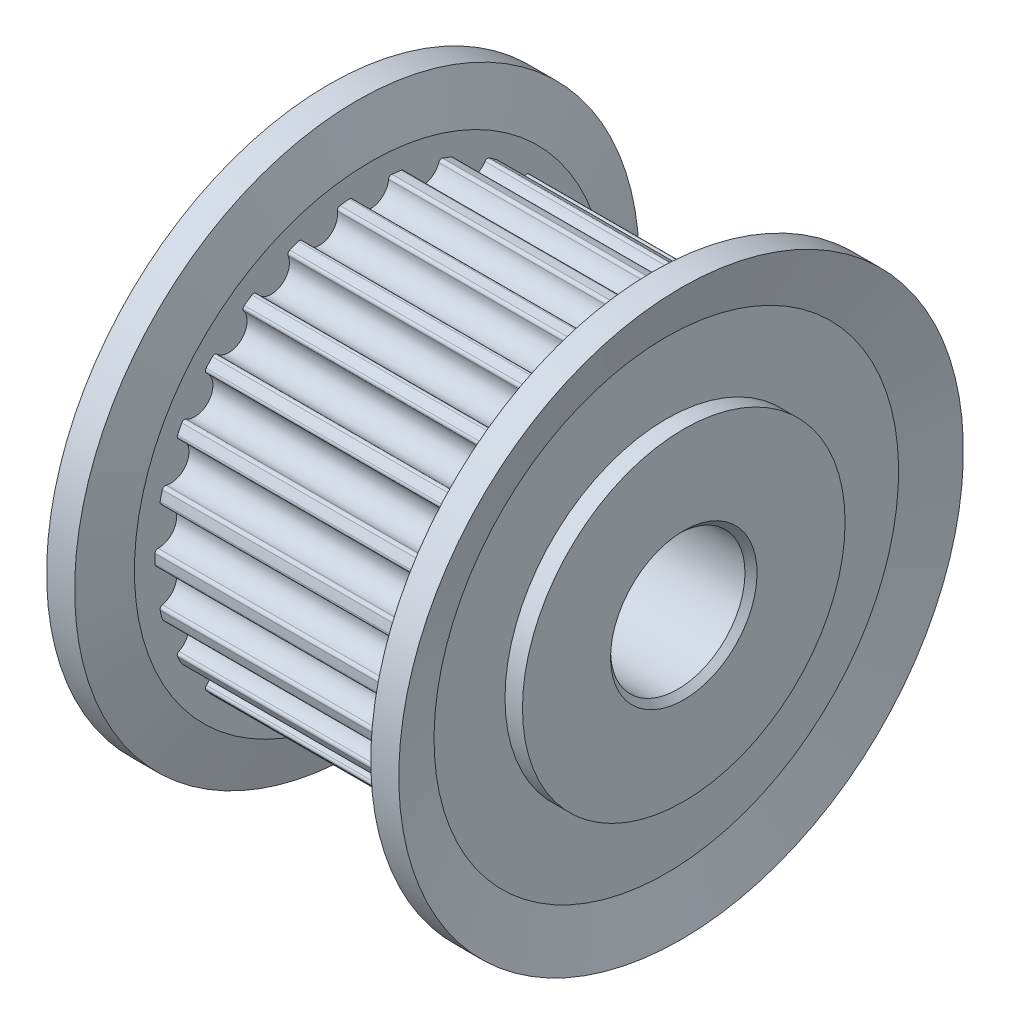
SolidWorks part; units mm, degrees
ref_plane "Front Plane" through (0, 0, 0) normal (0, 0, 1) x (1, 0, 0)
ref_plane "Top Plane" through (0, 0, 0) normal (0, 1, 0) x (1, 0, 0)
ref_plane "Right Plane" through (0, 0, 0) normal (1, 0, 0) x (0, 0, -1)
sketch "Sketch1" plane through (0, 0, 0) normal (0, 0, 1) x (1, 0, 0)
  line L2 (-6.65, 6) -> (-6.65, 2.725)
  line L3 (6.65, 2.725) -> (6.65, 6)
  line L4 (0, 0) -> (0, 10.275) construction
  line L5 (5, 8.02) -> (5, 8.7848)
  line L6 (-5, 8.02) -> (-5, 8.7848)
  line L43 (-6.425, 2.5) -> (6.425, 2.5)
  line L44 (-5, 8.275) -> (5, 8.275) construction
  line L45 (17.85, 0) -> (-17.85, 0) construction
  line L47 (-5, 7.27) -> (5, 7.27) construction
  line L48 (-5, 8.02) -> (5, 8.02)
  line L52 (-6.65, 2.725) -> (-6.425, 2.5)
  line L53 (-6, 8.64) -> (-6, 6)
  line L54 (-5, 6) -> (-6.65, 6)
  line L58 (6.65, 2.725) -> (6.425, 2.5)
  line L59 (6, 8.64) -> (6, 6)
  line L60 (5, 6) -> (6.65, 6)
  line L61 (-6.55, 10.5) -> (-6, 8.64)
  line L66 (6, 8.64) -> (6.55, 10.5)
  line L83 (5, 8.02) -> (5, 6)
  line L84 (5, 8.7848) -> (5.5072, 10.5)
  line L85 (6.55, 10.5) -> (5.5072, 10.5)
  line L86 (-5, 8.02) -> (-5, 6)
  line L87 (-5.5072, 10.5) -> (-5, 8.7848)
  line L88 (-6.55, 10.5) -> (-5.5072, 10.5)
  dimension "D5" = 0.225
  dimension "D6" = 0.225
  dimension "D7" = 12
  dimension "D8" = 10
  dimension "D9" = 13.3
  dimension "D10" = 16.04
  dimension "D11" = 21
  dimension "D12" = 1
  dimension "D13" = 1
  dimension "D14" = 17.28
  dimension "D15" = 17.5695
  dimension "D16" = 5
revolve "Revolve1" add sketch "Sketch1" angle 360 about L45 region at (0, 5.0871, 0)
sketch "Sketch5" plane through (-5, 0, -21.5) normal (-1, 0, 0) x (0, 0, 1)
  line L1 (19, 7.6204) -> (19, 7.8883)
  line L2 (21.5, 0) -> (21.5, 19.8172) construction
  line L3 (21.5, 0) -> (2.0173, 0) construction
  line L4 (24, 7.6204) -> (24, 7.8883)
  arc A6 (22.2949, 7.9805) -> (22.1718, 7.8795) centre (22.2838, 7.8686) ccw
  arc A7 (20.8282, 7.8795) -> (22.1718, 7.8795) centre (21.5, 7.945) ccw
  arc A8 (20.8282, 7.8795) -> (20.7051, 7.9805) centre (20.7162, 7.8686) ccw
  arc A9 (24, 7.6204) -> (22.2949, 7.9805) centre (21.5, 0) ccw
  arc A10 (24, 7.8883) -> (19, 7.8883) centre (21.5, 0) ccw
  arc A11 (20.7051, 7.9805) -> (19, 7.6204) centre (21.5, 0) ccw
  circle A12 centre (21.5, 0) radius 8.02 construction
  dimension "D2" = 8.275
  dimension "D3" = 5
  dimension "D5" = 0.675
  dimension "D6" = 0.1125
  dimension "D10" = 8.02
  dimension "D7" = 1.5676
  dimension "D8" = 7.945
  dimension "D9" = 7.8686
extrude "Cut-Extrude1" cut sketch "Sketch5" against normal through all
pattern_circular "CirPattern1" count 26 over 360 about axis through (17.85, 0, 0) along (1, 0, 0) of "Cut-Extrude1"
revolve "Revolve2" add sketch "Sketch1<4>" angle 360 about L45 region at (-5.6078, 8.2727, 0) region at (5.6078, 8.2727, 0)
sketch "Sketch1<4>" plane through (0, 0, 0) normal (0, 0, 1) x (1, 0, 0) same geometry as "Sketch1"
